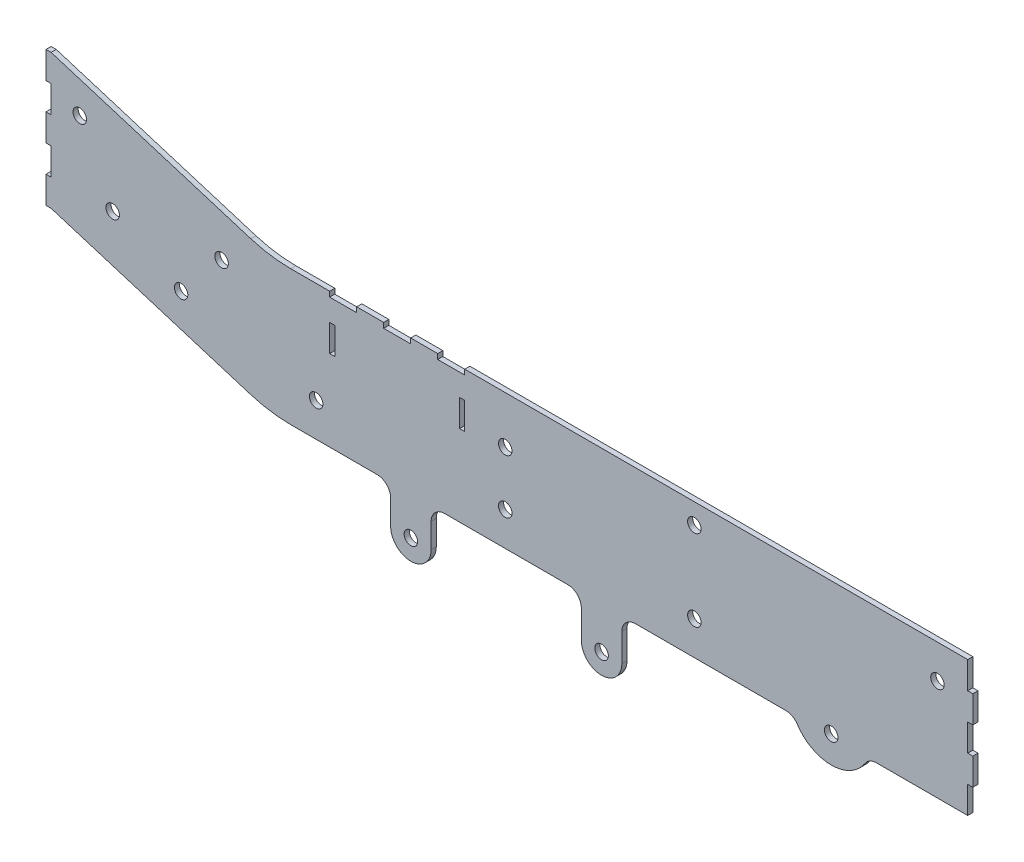
SolidWorks part; units mm, degrees
material "1060 Alloy"
ref_plane "Front Plane" through (0, 0, 0) normal (0, 0, 1) x (1, 0, 0)
ref_plane "Top Plane" through (0, 0, 0) normal (0, 1, 0) x (1, 0, 0)
ref_plane "Right Plane" through (0, 0, 0) normal (1, 0, 0) x (0, 0, -1)
sketch "Sketch2" plane through (0, 0, 0) normal (0, 0, 1) x (1, 0, 0)
  line L41 (-214.6997, -160.1998) -> (-26.8739, -218.0697)
  line L42 (10.5206, -223.6998) -> (91.8093, -223.6998)
  line L43 (104.5093, -236.3998) -> (104.5093, -259.4448)
  line L44 (142.6093, -259.4448) -> (142.6093, -236.3998)
  line L45 (155.3093, -223.6998) -> (271.0993, -223.6998)
  line L46 (283.7993, -236.3998) -> (283.7993, -262.6248)
  line L47 (321.8993, -262.6248) -> (321.8993, -236.3998)
  line L48 (334.5993, -223.6998) -> (476.2017, -223.6998)
  line L49 (561.2969, -223.6998) -> (656.7743, -223.6998)
  line L50 (656.7743, -223.6998) -> (656.7743, -198.2998)
  line L51 (656.7743, -198.2998) -> (651.9483, -198.2998)
  line L52 (651.9483, -198.2998) -> (651.9483, -172.8998)
  line L53 (651.9483, -172.8998) -> (656.7743, -172.8998)
  line L54 (656.7743, -172.8998) -> (656.7743, -147.4998)
  line L55 (656.7743, -147.4998) -> (651.9483, -147.4998)
  line L56 (651.9483, -147.4998) -> (651.9483, -122.0998)
  line L57 (651.9483, -122.0998) -> (656.7743, -122.0998)
  line L58 (656.7743, -122.0998) -> (656.7743, -96.6998)
  line L59 (656.7743, -96.6998) -> (174.1743, -96.6998)
  line L60 (174.1743, -96.6998) -> (174.1743, -101.5258)
  line L61 (174.1743, -101.5258) -> (148.7743, -101.5258)
  line L62 (148.7743, -101.5258) -> (148.7743, -96.6998)
  line L63 (148.7743, -96.6998) -> (123.3743, -96.6998)
  line L64 (123.3743, -96.6998) -> (123.3743, -101.5258)
  line L65 (123.3743, -101.5258) -> (97.9743, -101.5258)
  line L66 (97.9743, -101.5258) -> (97.9743, -96.6998)
  line L67 (97.9743, -96.6998) -> (72.5743, -96.6998)
  line L68 (72.5743, -96.6998) -> (72.5743, -101.5258)
  line L69 (72.5743, -101.5258) -> (47.1743, -101.5258)
  line L70 (47.1743, -101.5258) -> (47.1743, -96.6998)
  line L71 (47.1743, -96.6998) -> (10.5206, -96.6998)
  line L72 (-214.6997, -160.1998) -> (-26.8739, -218.0697)
  line L73 (-219.5257, -33.1998) -> (-219.5257, -58.5998)
  line L74 (-219.5257, -58.5998) -> (-214.6997, -58.5998)
  line L75 (-214.6997, -58.5998) -> (-214.6997, -83.9998)
  line L76 (-214.6997, -83.9998) -> (-219.5257, -83.9998)
  line L77 (-219.5257, -83.9998) -> (-219.5257, -109.3998)
  line L78 (-219.5257, -109.3998) -> (-214.6997, -109.3998)
  line L79 (-214.6997, -109.3998) -> (-214.6997, -134.7998)
  line L80 (-214.6997, -134.7998) -> (-219.5257, -134.7998)
  line L81 (-219.5257, -134.7998) -> (-219.5257, -160.1998)
  line L82 (-26.8739, -91.0697) -> (-214.6997, -33.1998)
  line L83 (10.5206, -223.6998) -> (91.8093, -223.6998)
  line L84 (104.5093, -236.3998) -> (104.5093, -259.4448)
  line L85 (142.6093, -259.4448) -> (142.6093, -236.3998)
  line L86 (155.3093, -223.6998) -> (271.0993, -223.6998)
  line L87 (283.7993, -236.3998) -> (283.7993, -262.6248)
  line L88 (321.8993, -262.6248) -> (321.8993, -236.3998)
  line L89 (334.5993, -223.6998) -> (476.2017, -223.6998)
  line L90 (561.2969, -223.6998) -> (656.7743, -223.6998)
  line L91 (656.7743, -223.6998) -> (656.7743, -198.2998)
  line L92 (656.7743, -198.2998) -> (651.9483, -198.2998)
  line L93 (651.9483, -198.2998) -> (651.9483, -172.8998)
  line L94 (651.9483, -172.8998) -> (656.7743, -172.8998)
  line L95 (656.7743, -172.8998) -> (656.7743, -147.4998)
  line L96 (656.7743, -147.4998) -> (651.9483, -147.4998)
  line L97 (651.9483, -147.4998) -> (651.9483, -122.0998)
  line L98 (651.9483, -122.0998) -> (656.7743, -122.0998)
  line L99 (656.7743, -122.0998) -> (656.7743, -96.6998)
  line L100 (656.7743, -96.6998) -> (174.1743, -96.6998)
  line L101 (174.1743, -96.6998) -> (174.1743, -101.5258)
  line L102 (174.1743, -101.5258) -> (148.7743, -101.5258)
  line L103 (148.7743, -101.5258) -> (148.7743, -96.6998)
  line L104 (148.7743, -96.6998) -> (123.3743, -96.6998)
  line L105 (123.3743, -96.6998) -> (123.3743, -101.5258)
  line L106 (123.3743, -101.5258) -> (97.9743, -101.5258)
  line L107 (97.9743, -101.5258) -> (97.9743, -96.6998)
  line L108 (97.9743, -96.6998) -> (72.5743, -96.6998)
  line L109 (72.5743, -96.6998) -> (72.5743, -101.5258)
  line L110 (72.5743, -101.5258) -> (47.1743, -101.5258)
  line L111 (47.1743, -101.5258) -> (47.1743, -96.6998)
  line L112 (47.1743, -96.6998) -> (10.5206, -96.6998)
  line L113 (-26.8739, -91.0697) -> (-214.6997, -33.1998)
  line L114 (-219.5257, -33.1998) -> (-219.5257, -58.5998)
  line L115 (-219.5257, -58.5998) -> (-214.6997, -58.5998)
  line L116 (-214.6997, -58.5998) -> (-214.6997, -83.9998)
  line L117 (-214.6997, -83.9998) -> (-219.5257, -83.9998)
  line L118 (-219.5257, -83.9998) -> (-219.5257, -109.3998)
  line L119 (-219.5257, -109.3998) -> (-214.6997, -109.3998)
  line L120 (-214.6997, -109.3998) -> (-214.6997, -134.7998)
  line L121 (-214.6997, -134.7998) -> (-219.5257, -134.7998)
  line L122 (-219.5257, -134.7998) -> (-219.5257, -160.1998)
  line L412 (-214.6997, -33.1998) -> (-219.5257, -33.1998)
  line L413 (-214.6997, -33.1998) -> (-219.5257, -33.1998)
  line L414 (-219.5257, -160.1998) -> (-214.6997, -160.1998)
  line L415 (-219.5257, -160.1998) -> (-214.6997, -160.1998)
  arc A11 (-26.8739, -218.0697) -> (10.5206, -223.6998) centre (10.5206, -96.6998) ccw
  arc A12 (104.5093, -236.3998) -> (91.8093, -223.6998) centre (91.8093, -236.3998) ccw
  arc A13 (104.5093, -259.4448) -> (142.6093, -259.4448) centre (123.5593, -259.4448) ccw
  arc A14 (155.3093, -223.6998) -> (142.6093, -236.3998) centre (155.3093, -236.3998) ccw
  arc A15 (283.7993, -236.3998) -> (271.0993, -223.6998) centre (271.0993, -236.3998) ccw
  arc A16 (283.7993, -262.6248) -> (321.8993, -262.6248) centre (302.8493, -262.6248) ccw
  arc A17 (334.5993, -223.6998) -> (321.8993, -236.3998) centre (334.5993, -236.3998) ccw
  arc A18 (486.8386, -229.461) -> (476.2017, -223.6998) centre (476.2017, -236.3998) ccw
  arc A19 (486.8386, -229.461) -> (550.66, -229.461) centre (518.7493, -208.6448) ccw
  arc A20 (561.2969, -223.6998) -> (550.66, -229.461) centre (561.2969, -236.3998) ccw
  arc A21 (-26.8739, -218.0697) -> (10.5206, -223.6998) centre (10.5206, -96.6998) ccw
  arc A22 (-26.8739, -91.0697) -> (10.5206, -96.6998) centre (10.5206, 30.3002) ccw
  arc A23 (104.5093, -236.3998) -> (91.8093, -223.6998) centre (91.8093, -236.3998) ccw
  arc A24 (104.5093, -259.4448) -> (142.6093, -259.4448) centre (123.5593, -259.4448) ccw
  arc A25 (155.3093, -223.6998) -> (142.6093, -236.3998) centre (155.3093, -236.3998) ccw
  arc A26 (283.7993, -236.3998) -> (271.0993, -223.6998) centre (271.0993, -236.3998) ccw
  arc A27 (283.7993, -262.6248) -> (321.8993, -262.6248) centre (302.8493, -262.6248) ccw
  arc A28 (334.5993, -223.6998) -> (321.8993, -236.3998) centre (334.5993, -236.3998) ccw
  arc A29 (486.8386, -229.461) -> (476.2017, -223.6998) centre (476.2017, -236.3998) ccw
  arc A30 (486.8386, -229.461) -> (550.66, -229.461) centre (518.7493, -208.6448) ccw
  arc A31 (561.2969, -223.6998) -> (550.66, -229.461) centre (561.2969, -236.3998) ccw
  arc A32 (-26.8739, -91.0697) -> (10.5206, -96.6998) centre (10.5206, 30.3002) ccw
  circle A56 centre (390.0743, -191.9498) radius 6.35
  circle A57 centre (390.0743, -191.9498) radius 6.35
  circle A58 centre (390.0743, -115.7498) radius 6.35
  circle A59 centre (390.0743, -115.7498) radius 6.35
  circle A60 centre (518.7493, -221.3448) radius 6.35
  circle A61 centre (518.7493, -221.3448) radius 6.35
  circle A62 centre (618.6743, -128.4498) radius 6.35
  circle A63 centre (618.6743, -128.4498) radius 6.35
  circle A64 centre (302.8493, -262.6248) radius 6.35
  circle A65 centre (302.8493, -262.6248) radius 6.35
  circle A66 centre (212.2743, -191.9498) radius 6.35
  circle A67 centre (212.2743, -191.9498) radius 6.35
  circle A68 centre (212.2743, -141.1498) radius 6.35
  circle A69 centre (212.2743, -141.1498) radius 6.35
  circle A70 centre (123.5593, -259.4448) radius 6.35
  circle A71 centre (123.5593, -259.4448) radius 6.35
  circle A72 centre (34.4743, -191.9498) radius 6.35
  circle A73 centre (34.4743, -191.9498) radius 6.35
  circle A74 centre (-92.5257, -166.5498) radius 6.35
  circle A75 centre (-92.5257, -166.5498) radius 6.35
  circle A76 centre (-156.8507, -133.7248) radius 6.35
  circle A77 centre (-156.8507, -133.7248) radius 6.35
  circle A78 centre (-54.4257, -122.0998) radius 6.35
  circle A79 centre (-54.4257, -122.0998) radius 6.35
  circle A80 centre (-187.7757, -71.2998) radius 6.35
  circle A81 centre (-187.7757, -71.2998) radius 6.35
  dimension "D1" = 0
  dimension "D2" = 0
  dimension "D3" = 0
  dimension "D4" = 0
  dimension "D5" = 0
  dimension "D6" = 0
  dimension "D7" = 0
  dimension "D8" = 0
  dimension "D9" = 0
  dimension "D10" = 0
  dimension "D11" = 0
  dimension "D12" = 0
  dimension "D13" = 0
  dimension "D14" = 0
extrude "base" add sketch "Sketch2" along normal blind 4.826
sketch "Sketch3" plane through (0, 0, 4.826) normal (0, 0, 1) x (1, 0, 0)
  line L0 (47.1743, -101.5258) -> (47.1743, -96.6998) construction
  line L1 (169.3483, -122.0998) -> (174.1743, -122.0998)
  line L2 (169.3483, -122.0998) -> (169.3483, -147.4998)
  line L3 (169.3483, -147.4998) -> (174.1743, -147.4998)
  line L4 (174.1743, -122.0998) -> (174.1743, -147.4998)
  line L5 (47.1743, -122.0998) -> (52.0003, -122.0998)
  line L6 (47.1743, -122.0998) -> (47.1743, -147.4998)
  line L7 (47.1743, -147.4998) -> (52.0003, -147.4998)
  line L8 (52.0003, -122.0998) -> (52.0003, -147.4998)
  line L9 (174.1743, -96.6998) -> (174.1743, -101.5258) construction
  line L10 (97.9743, -96.6998) -> (72.5743, -96.6998) construction
  dimension "D1" = 4.826
  dimension "D2" = 25.4
  dimension "D3" = 25.4
extrude "center support vertical holes" cut sketch "Sketch3" against normal through all
sketch "Sketch4" plane through (656.7743, 0, 0) normal (1, 0, 0) x (0, 0, -1)
  line L0 (0, -122.0998) -> (0, -96.6998) construction
  line L1 (0, -96.6998) -> (-4.826, -96.6998) construction
  line L2 (-4.826, -96.6998) -> (-4.826, -122.0998) construction
  line L3 (-4.826, -122.0998) -> (0, -122.0998) construction
  line L4 (0, -172.8998) -> (0, -147.4998) construction
  line L5 (0, -147.4998) -> (-4.826, -147.4998) construction
  line L6 (-4.826, -147.4998) -> (-4.826, -172.8998) construction
  line L7 (-4.826, -172.8998) -> (0, -172.8998) construction
  line L8 (0, -223.6998) -> (0, -198.2998) construction
  line L9 (0, -198.2998) -> (-4.826, -198.2998) construction
  line L10 (-4.826, -198.2998) -> (-4.826, -223.6998) construction
  line L11 (-4.826, -223.6998) -> (0, -223.6998) construction
  line L12 (0, -122.0998) -> (0, -96.6998)
  line L13 (0, -96.6998) -> (-4.826, -96.6998)
  line L14 (-4.826, -96.6998) -> (-4.826, -122.0998)
  line L15 (-4.826, -122.0998) -> (0, -122.0998)
  line L16 (0, -172.8998) -> (0, -147.4998)
  line L17 (0, -147.4998) -> (-4.826, -147.4998)
  line L18 (-4.826, -147.4998) -> (-4.826, -172.8998)
  line L19 (-4.826, -172.8998) -> (0, -172.8998)
  line L20 (0, -223.6998) -> (0, -198.2998)
  line L21 (0, -198.2998) -> (-4.826, -198.2998)
  line L22 (-4.826, -198.2998) -> (-4.826, -223.6998)
  line L23 (-4.826, -223.6998) -> (0, -223.6998)
extrude "Cut-Extrude2" cut sketch "Sketch4" against normal blind 9.652
equation "\"sheet width\"= .19"
equation "\"width\"= 24.5"
equation "\"length\"= 34.5"
equation "\"standoff hole size\"= .5"
equation "\"ground clearence\"= 3"
equation "\"small drive pulley\"= 74.55mm"
equation "\"large drive pulley\"= 150.95mm"
equation "\"drive axle hole size\"= .5"
equation "\"front pulley clearence\"= 1"
equation "\"center support location\"= 19"
equation "\"D1@Sketch3\"=\"sheet width\""
equation "\"D1@base\"=\"sheet width\""
equation "\"D1@Cut-Extrude2\"=\"sheet width\"*2"
